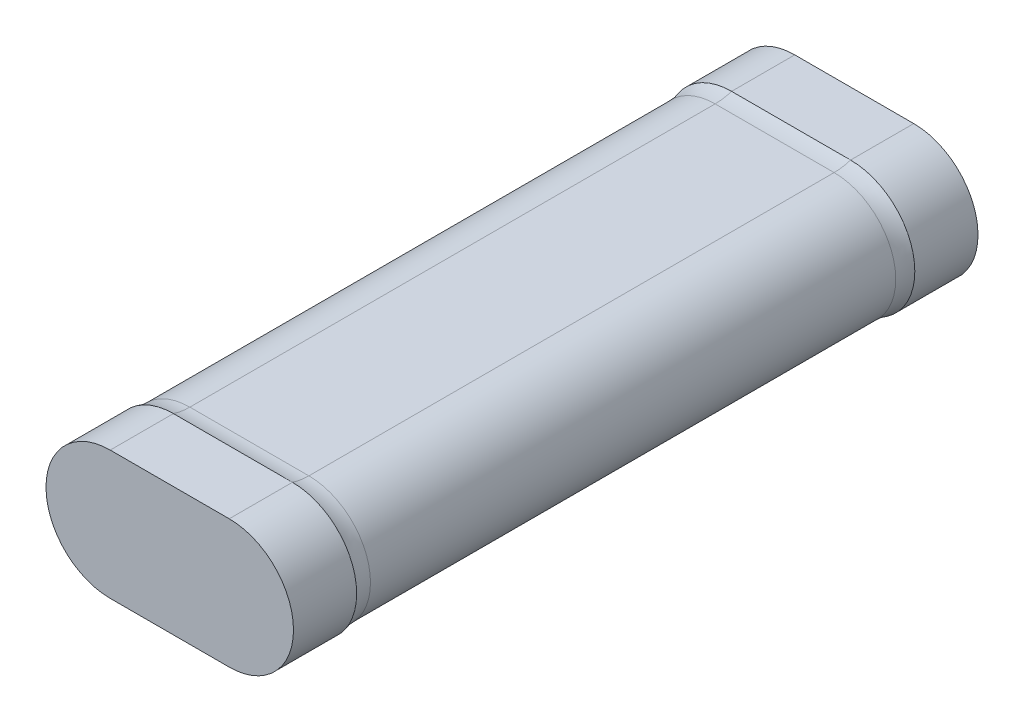
SolidWorks part; units mm, degrees
ref_plane "Front Plane" through (0, 0, 0) normal (0, 0, 1) x (1, 0, 0)
ref_plane "Top Plane" through (0, 0, 0) normal (0, 1, 0) x (1, 0, 0)
ref_plane "Right Plane" through (0, 0, 0) normal (1, 0, 0) x (0, 0, -1)
sketch "Sketch1" plane through (0, 0, 0) normal (0, 0, 1) x (1, 0, 0)
  line L0 (-11.3, 0) -> (11.3, 0) construction
  line L1 (44.8678, 0) -> (-37.6971, 0) construction
  line L2 (-11.3, 11.7) -> (11.3, 11.7)
  line L3 (-11.3, -11.7) -> (11.3, -11.7)
  line L4 (0, -18.5887) -> (0, 20.3426) construction
  arc A0 (-11.3, 11.7) -> (-11.3, -11.7) centre (-11.3, 0) ccw
  arc A1 (11.3, -11.7) -> (11.3, 11.7) centre (11.3, 0) ccw
  point P5 (0, 0)
  point P12 (23, 0)
  point P13 (-23, 0)
  dimension "D1" = 46
  dimension "D2" = 23.4
extrude "Boss-Extrude1" add sketch "Sketch1" along normal blind 65 and the other way blind 65
sketch "Sketch2" plane through (0, 0, 65) normal (0, 0, 1) x (1, 0, 0)
  line L0 (-11.3, 0) -> (11.3, 0) construction
  line L1 (-11.3, 12.2) -> (11.3, 12.2)
  line L2 (-11.3, -12.2) -> (11.3, -12.2)
  arc A0 (-11.3, 12.2) -> (-11.3, -12.2) centre (-11.3, 0) ccw
  arc A1 (11.3, -12.2) -> (11.3, 12.2) centre (11.3, 0) ccw
  point P4 (0, 0)
  dimension "D1" = 24.4
extrude "Boss-Extrude2" add sketch "Sketch2" against normal blind 12
mirror "Mirror1" about plane through (0, 0, 0) normal (0, 0, 1) of "Boss-Extrude2"
fillet "Fillet1" radius 10 4 edges at (0, -11.7, 53) (23, 0, 53) (0, 11.7, 53) (-23, 0, 53)
fillet "Fillet2" radius 10 4 edges at (23, 0, -53) (0, -11.7, -53) (-23, 0, -53) (0, 11.7, -53)
